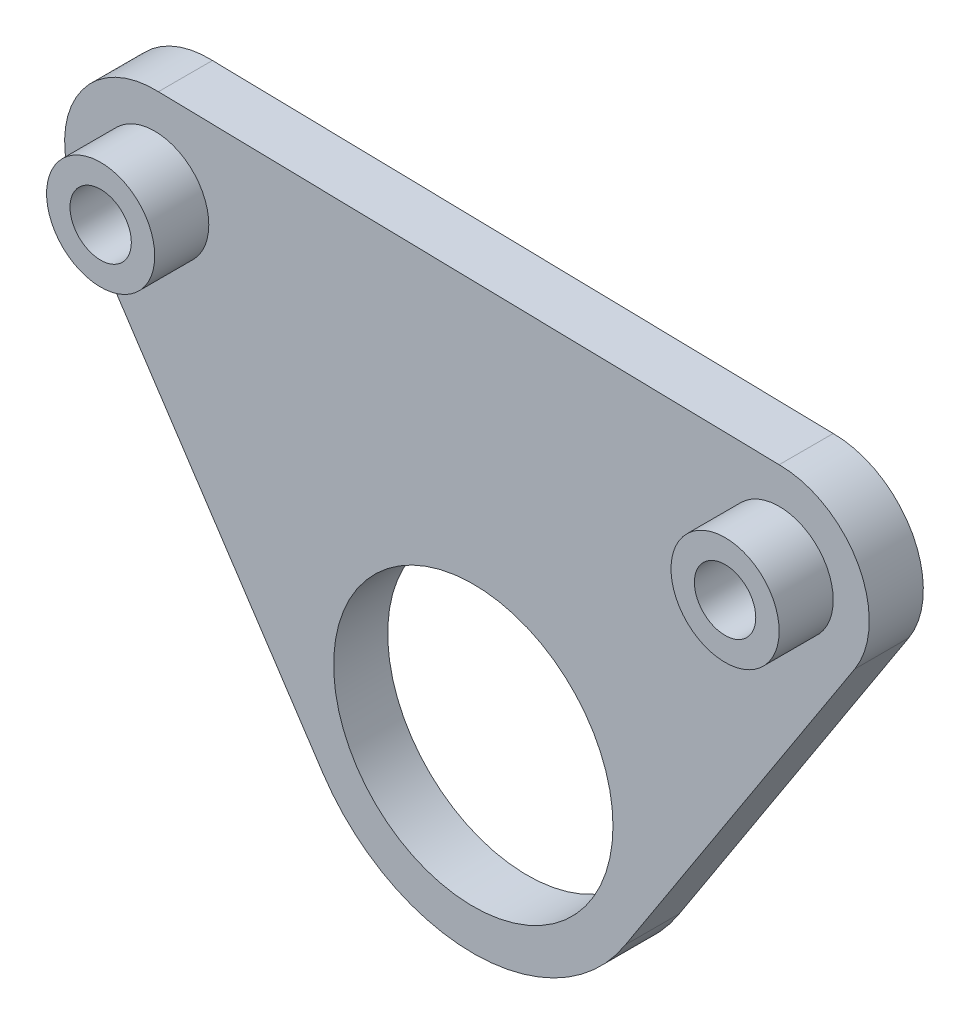
SolidWorks part; units mm, degrees
ref_plane "Front Plane" through (0, 0, 0) normal (0, 0, 1) x (1, 0, 0)
ref_plane "Top Plane" through (0, 0, 0) normal (0, 1, 0) x (1, 0, 0)
ref_plane "Right Plane" through (0, 0, 0) normal (1, 0, 0) x (0, 0, -1)
sketch "Sketch1" plane through (0, 0, 0) normal (0, 0, 1) x (1, 0, 0)
  line L0 (0, 0) -> (0, -44.3691) construction
  line L1 (0, 0) -> (0, 32.675) construction
  line L2 (0, -44.3691) -> (-72.2288, 27.8597) construction
  line L3 (0, 0) -> (-40.7025, -40.7025) construction
  line L4 (0, 0) -> (33.9411, 33.9411) construction
  line L5 (0, 0) -> (-35.3553, 35.3553) construction
  line L6 (-21.8489, 14.9207) -> (-8.3424, -5.514)
  line L7 (-17.4737, 22.6735) -> (16.9706, 21.9706)
  line L8 (8.4349, -5.3714) -> (21.165, 14.2491)
  circle A0 centre (0, 0) radius 7.75
  arc A1 (-8.3424, -5.514) -> (8.4349, -5.3714) centre (0, 0) ccw
  circle A2 centre (-17.6777, 17.6777) radius 1.7025
  circle A3 centre (16.9706, 16.9706) radius 1.7025
  circle A4 centre (-17.6777, 17.6777) radius 3
  circle A5 centre (16.9706, 16.9706) radius 3
  arc A6 (-17.4737, 22.6735) -> (-21.8489, 14.9207) centre (-17.6777, 17.6777) ccw
  arc A7 (21.165, 14.2491) -> (16.9706, 21.9706) centre (16.9706, 16.9706) ccw
  dimension "D1" = 15.5
  dimension "D2" = 20
  dimension "D4" = 3.405
  dimension "D6" = 3.405
  dimension "D7" = 6
  dimension "D8" = 6
  dimension "D9" = 10
  dimension "D10" = 10
  dimension "D3" = 25
  dimension "D5" = 24
extrude "Boss-Extrude3" add sketch "Sketch1" along normal blind 3 contours L8 A7 L7 A6 L6 A1 A0 A4 A5 region at (-0.3618, 11.2981, 0)
sketch "Sketch3" plane through (0, 0, 3) normal (0, 0, 1) x (1, 0, 0)
  circle A0 centre (-17.6777, 17.6777) radius 3
  circle A1 centre (-17.6777, 17.6777) radius 1.7025
  circle A2 centre (16.9706, 16.9706) radius 3
  circle A3 centre (16.9706, 16.9706) radius 1.7025
  dimension "D1" = 3.405
  dimension "D2" = 3.405
extrude "Boss-Extrude4" add sketch "Sketch3" along normal blind 3 and the other way blind 3
sketch "Sketch4" plane through (0, 0, 0) normal (0, 0, -1) x (-1, 0, 0)
  text T0 "<b>R</b>"
extrude "Cut-Extrude2" cut sketch "Sketch4" against normal blind 0.5
